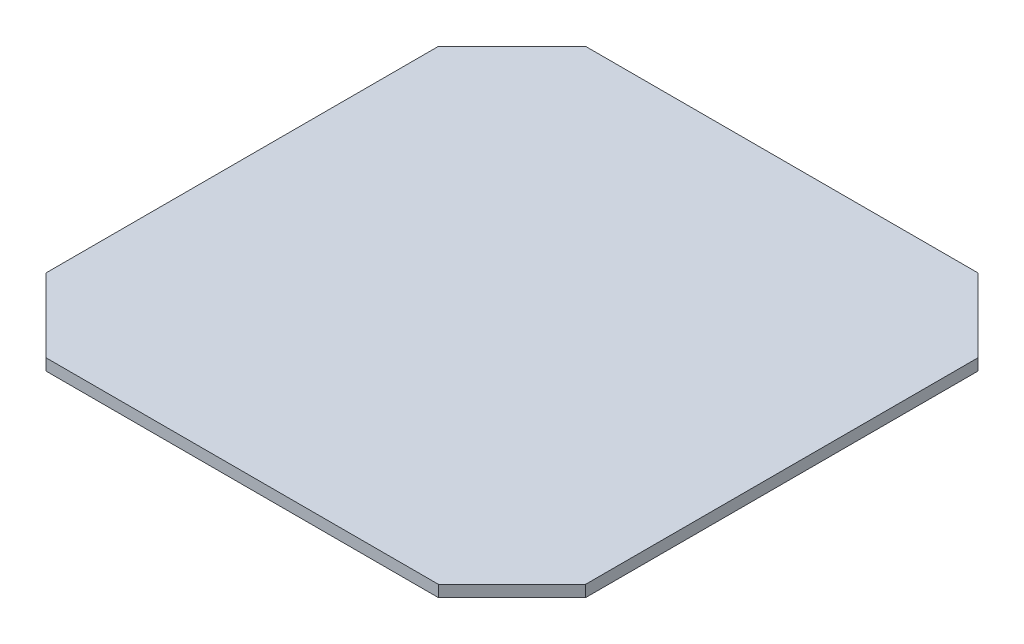
SolidWorks part; units mm, degrees
material "ABS PC"
ref_plane "Front Plane" through (0, 0, 0) normal (0, 0, 1) x (1, 0, 0)
ref_plane "Top Plane" through (0, 0, 0) normal (0, 1, 0) x (1, 0, 0)
ref_plane "Right Plane" through (0, 0, 0) normal (1, 0, 0) x (0, 0, -1)
sketch "Sketch1" plane through (0, 0, 0) normal (0, 1, 0) x (1, 0, 0)
  line L0 (-23.364, 17) -> (-17, 23.364)
  line L1 (-17, -23.364) -> (17, -23.364)
  line L2 (-23.364, -17) -> (-23.364, 17)
  line L3 (-17, 23.364) -> (17, 23.364)
  line L4 (23.364, -17) -> (23.364, 17)
  line L5 (-20.182, -20.182) -> (20.182, 20.182) construction
  line L6 (-20.182, 20.182) -> (20.182, -20.182) construction
  line L7 (-23.364, -17) -> (-17, -23.364)
  line L8 (17, -23.364) -> (23.364, -17)
  line L9 (17, 23.364) -> (23.364, 17)
  point P0 (0, 0)
  dimension "D1" = 34
  dimension "D2" = 34
  dimension "D3" = 135
  dimension "D4" = 135
  dimension "D5" = 9
  dimension "D6" = 135
extrude "Boss-Extrude1" add sketch "Sketch1" along normal blind 1
